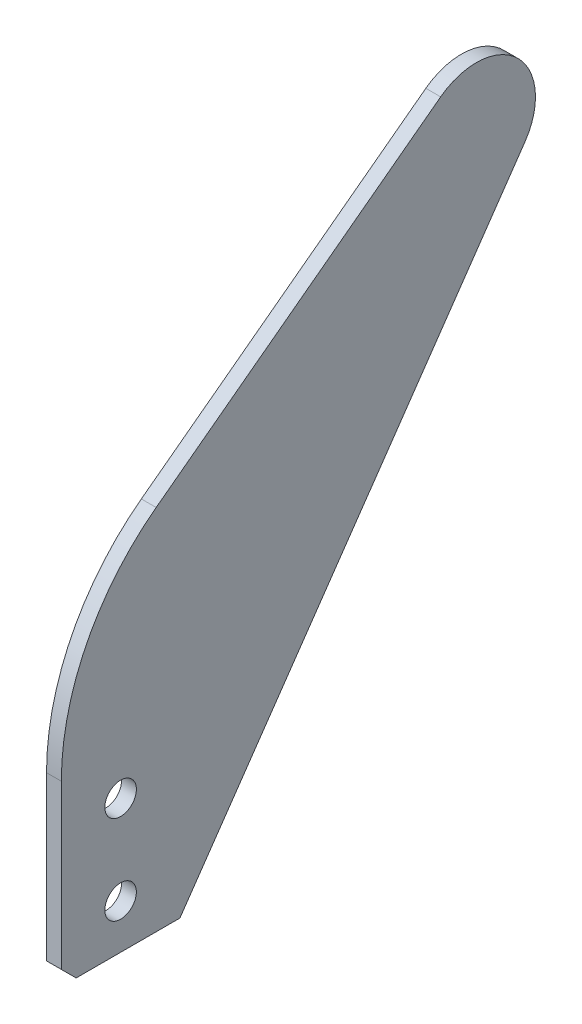
SolidWorks part; units mm, degrees
ref_plane "Front Plane" through (0, 0, 0) normal (0, 0, 1) x (1, 0, 0)
ref_plane "Top Plane" through (0, 0, 0) normal (0, 1, 0) x (1, 0, 0)
ref_plane "Right Plane" through (0, 0, 0) normal (1, 0, 0) x (0, 0, -1)
sketch "Sketch1" plane through (0, 0, 0) normal (1, 0, 0) x (0, 0, -1)
  line L0 (0, 0) -> (0, 38.1)
  line L1 (0, 0) -> (25.4, 0)
  line L2 (25.4, 0) -> (99.3502, 107.0832)
  line L4 (81.28, 124.46) -> (20.32, 78.74)
  arc A0 (20.32, 78.74) -> (0, 38.1) centre (50.8, 38.1) ccw
  arc A1 (81.28, 124.46) -> (99.3502, 107.0832) centre (88.9, 114.3) cw
  circle A2 centre (12.7, 9.525) radius 3.3782
  circle A3 centre (12.7, 28.575) radius 3.3782
  point P13 (0, 0)
  point P14 (12.7, 0)
  dimension "D2" = 50.8
  dimension "D3" = 12.7
  dimension "D7" = 6.7564
  dimension "D8" = 12.7
  dimension "D9" = 9.525
  dimension "D1" = 25.4
  dimension "D4" = 88.9
  dimension "D5" = 114.3
  dimension "D6" = 38.1
  dimension "D10" = 9.525
extrude "Boss-Extrude1" add sketch "Sketch1" along normal blind 3.175
chamfer "Chamfer1" distance 3.175 angle 45 1 edges at (1.5875, 0, 0)
